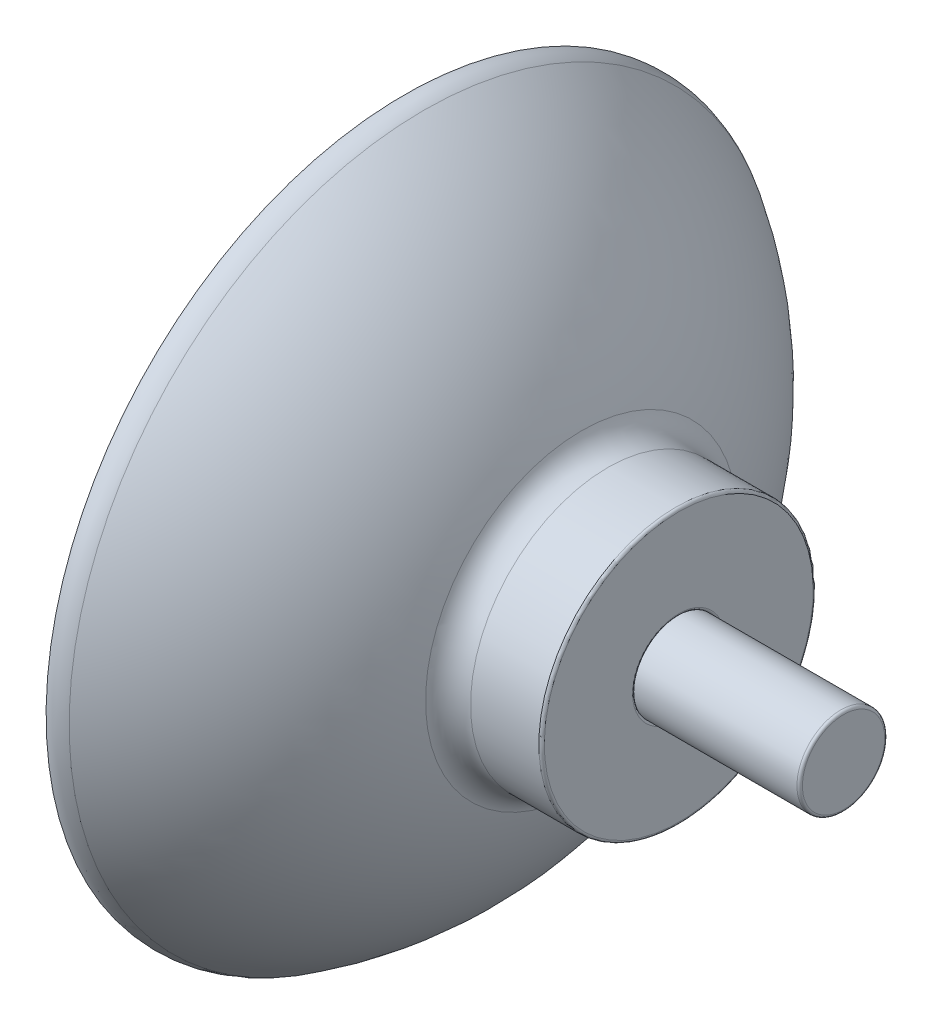
SolidWorks part; units mm, degrees
ref_plane "Front Plane" through (0, 0, 0) normal (0, 0, 1) x (1, 0, 0)
ref_plane "Top Plane" through (0, 0, 0) normal (0, 1, 0) x (1, 0, 0)
ref_plane "Right Plane" through (0, 0, 0) normal (1, 0, 0) x (0, 0, -1)
sketch "Sketch1" plane through (0, 0, 0) normal (0, 0, 1) x (1, 0, 0)
  line L0 (0, 0) -> (-10, 0) construction
  line L1 (0, 0) -> (5, 0) construction
  line L2 (0, 0) -> (0, 7.5)
  line L3 (0, 7.5) -> (5, 7.5)
  line L4 (5, 0) -> (5, 7.5)
  line L5 (2, 0) -> (4, 0) construction
  line L6 (2, 0) -> (2, 4.75)
  line L7 (2, 4.75) -> (4, 4.75)
  line L8 (4, 0) -> (4, 4.75)
  line L9 (-10, 0) -> (-10, 20) construction
  line L10 (-10, 20) -> (-10, 19.5)
  line L11 (2, 0) -> (0, 0)
  line L12 (5, 0) -> (4, 0)
  line L13 (0, 4) -> (0, 7.5)
  line L14 (4, 2.375) -> (5, 2.375)
  arc A0 (-10, 20) -> (0, 7.5) centre (-19.3122, 2.3002) cw
  arc A1 (-10, 19.5) -> (0, 4) centre (-21.7836, 0.9219) cw
  dimension "D8" = 20
  dimension "D11" = 22
  dimension "D1" = 5
  dimension "D2" = 7.5
  dimension "D3" = 2
  dimension "D4" = 1
  dimension "D5" = 4.75
  dimension "D6" = 10
  dimension "D7" = 20
  dimension "D9" = 0.5
  dimension "D10" = 3.5
revolve "Revolve2" add sketch "Sketch1" angle 360 about L0 region at (0.0901, 2, 0)
fillet "Fillet1" radius 0.15 5 edges at (4, 2.375, 0) (5, 2.375, 0) (5, 7.5, 0) (-10, 19.5, 0) (0, 4, 0)
fillet "Fillet2" radius 1.5 2 edges at (-10, 20, 0) (0, 7.5, 0)
sketch "Sketch2" plane through (0, 0, 0) normal (0, 1, 0) x (1, 0, 0)
  line L0 (2, 0) -> (2, 4.76)
  line L1 (2, -4.75) -> (2, 4.75) construction
  line L2 (2, 4.76) -> (4.0072, 4.76)
  line L3 (4.0072, 4.76) -> (4.0072, 2.4)
  line L4 (4.0072, 2.4) -> (14.0072, 2.4)
  line L5 (14.0072, 2.4) -> (14.0072, 0)
  line L6 (14.0072, 0) -> (2, 0)
  dimension "D1" = 10
  dimension "D2" = 2.4
  dimension "D3" = 2.36
revolve "Revolve3" add sketch "Sketch2" angle 360 about L6
fillet "Fillet3" radius 0.15 1 edges at (14.0072, 0, -2.4)
